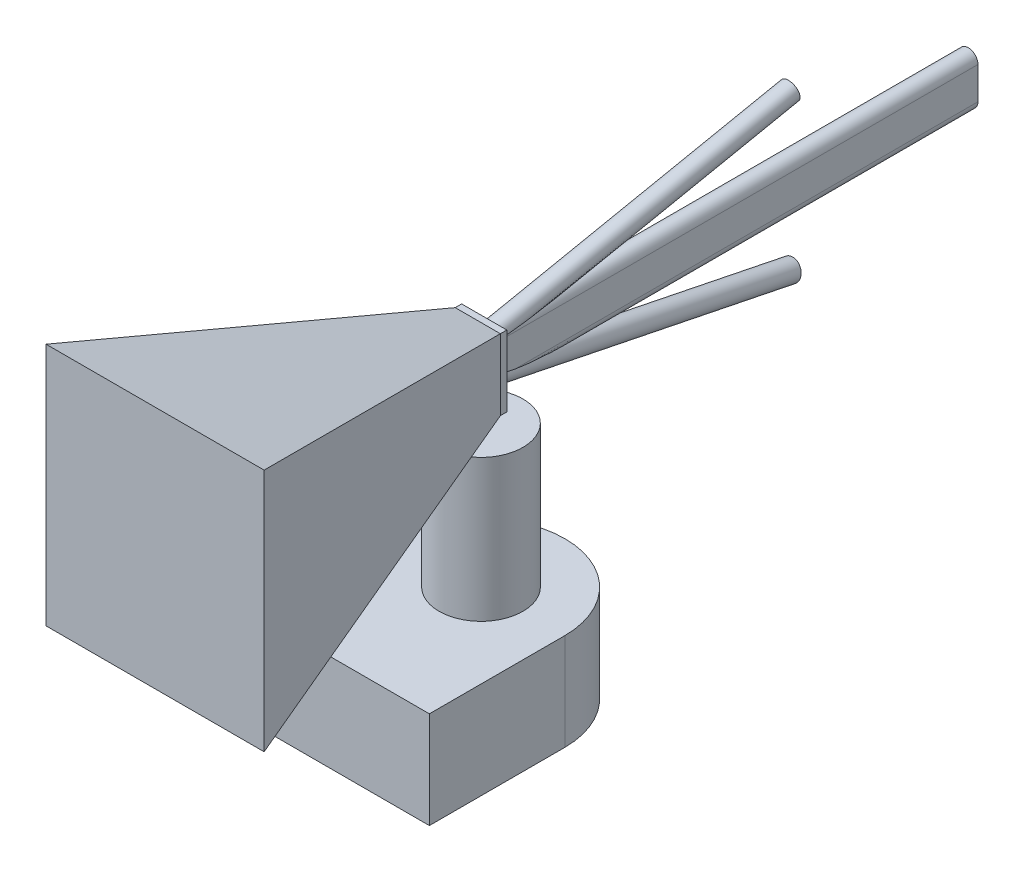
SolidWorks part; units mm, degrees
ref_plane "Front Plane" through (0, 0, 0) normal (0, 0, 1) x (1, 0, 0)
ref_plane "Top Plane" through (0, 0, 0) normal (0, 1, 0) x (1, 0, 0)
ref_plane "Right Plane" through (0, 0, 0) normal (1, 0, 0) x (0, 0, -1)
sketch "Sketch1" plane through (0, 0, 0) normal (0, 1, 0) x (1, 0, 0)
  line L0 (-13, 0) -> (-13, -21)
  line L1 (-13, -21) -> (13, -21)
  line L2 (13, -21) -> (13, 0)
  arc A0 (13, 0) -> (-13, 0) centre (0, 0) ccw
  point P6 (0, 13)
  dimension "D1" = 26
  dimension "D2" = 34
extrude "Boss-Extrude1" add sketch "Sketch1" along normal blind 15
sketch "Sketch2" plane through (0, 15, 0) normal (0, 1, 0) x (1, 0, 0)
  circle A0 centre (0, 0) radius 6.5
  dimension "D1" = 13
extrude "Boss-Extrude2" add sketch "Sketch2" along normal blind 22
sketch "Sketch3" plane through (0, 37, 0) normal (0, 1, 0) x (1, 0, 0)
  circle A0 centre (0, 0) radius 1
  dimension "D1" = 2
extrude "Boss-Extrude3" add sketch "Sketch3" along normal blind 3
sketch "Sketch4" plane through (0, 40, 0) normal (0, 1, 0) x (1, 0, 0)
  line L1 (-3.5, 0.5) -> (3.5, 0.5)
  line L2 (-3.5, 0.5) -> (-3.5, -0.5)
  line L3 (-3.5, -0.5) -> (3.5, -0.5)
  line L4 (3.5, 0.5) -> (3.5, -0.5)
  line L5 (-3.5, 0.5) -> (3.5, -0.5) construction
  line L6 (-3.5, -0.5) -> (3.5, 0.5) construction
  point P0 (0, 0)
  dimension "D1" = 1
  dimension "D2" = 7
extrude "Boss-Extrude4" add sketch "Sketch4" along normal blind 11
sketch "Sketch5" plane through (0, 0, 0.5) normal (0, 0, 1) x (1, 0, 0)
  circle A0 centre (0, 45.8701) radius 1.5
  dimension "D1" = 3
extrude "Boss-Extrude5" add sketch "Sketch5" along normal blind 20
sketch "Sketch6" plane through (0, 0, -0.5) normal (0, 0, -1) x (-1, 0, 0)
  line L0 (0, 48.1245) -> (0, 43.1245) construction
  line L1 (1.5, 48.1245) -> (1.5, 43.1245)
  line L2 (-1.5, 48.1245) -> (-1.5, 43.1245)
  arc A0 (1.5, 48.1245) -> (-1.5, 48.1245) centre (0, 48.1245) ccw
  arc A1 (-1.5, 43.1245) -> (1.5, 43.1245) centre (0, 43.1245) ccw
  point P2 (0, 45.6245)
  dimension "D1" = 3
  dimension "D2" = 5
extrude "Boss-Extrude6" add sketch "Sketch6" along normal blind 75
ref_plane "Plane1" through (0, 1.9294, 9.4835) normal (0, -0.1994, -0.9799) x (-1, 0, 0)
sketch "Sketch7" plane through (0, 1.9294, 9.4835) normal (0, -0.1994, -0.9799) x (-1, 0, 0)
  circle A0 centre (0, 42.4779) radius 1.5894
extrude "Boss-Extrude7" add sketch "Sketch7" along normal blind 50
ref_plane "Plane2" through (0, 1.6876, -8.2947) normal (0, 0.1994, -0.9799) x (-1, 0, 0)
sketch "Sketch8" plane through (0, 1.6876, -8.2947) normal (0, 0.1994, -0.9799) x (-1, 0, 0)
  line L0 (0, 49.0363) -> (0, 45.049) construction
  circle A0 centre (0, 47.0197) radius 1.5
  dimension "D1" = 3
extrude "Boss-Extrude8" add sketch "Sketch8" along normal blind 50 contours A0
sketch "Sketch9" plane through (0, 0, 0.5) normal (0, 0, 1) x (1, 0, 0)
  line L1 (3.5, 51) -> (-3.5, 51)
  line L2 (3.5, 51) -> (3.5, 40)
  line L3 (3.5, 40) -> (-3.5, 40)
  line L4 (-3.5, 51) -> (-3.5, 40)
extrude "Boss-Extrude9" add sketch "Sketch9" along normal blind 50 draft 15 draft outward yes
